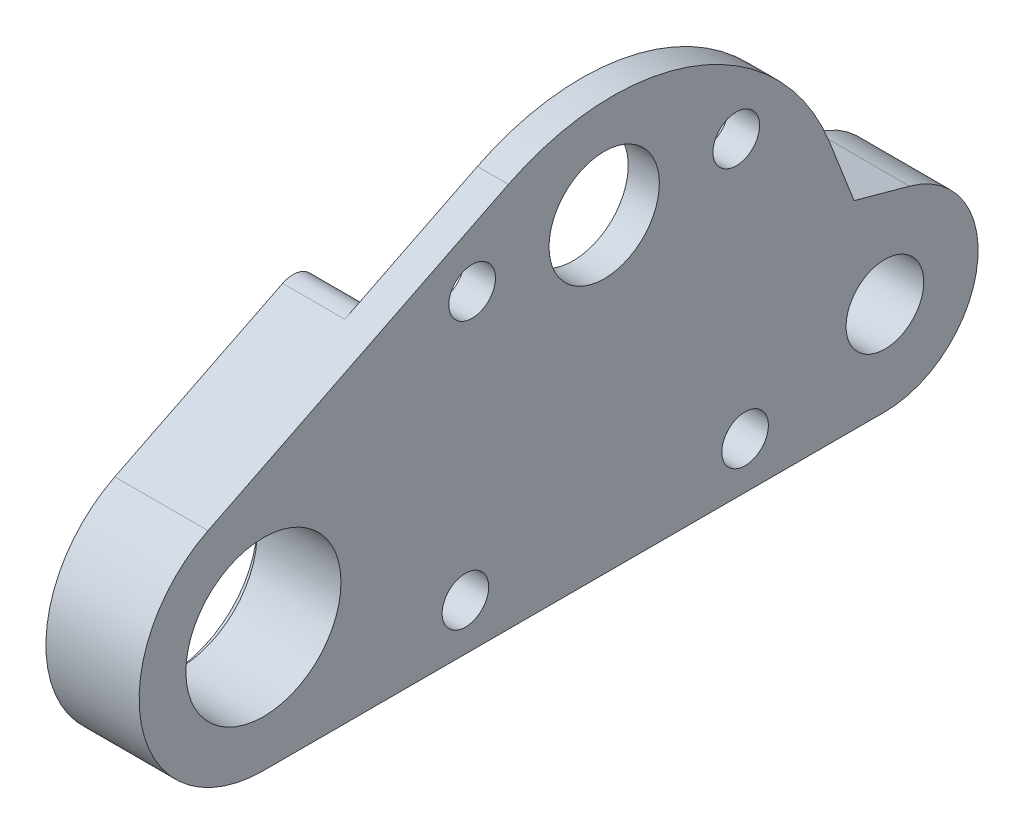
SolidWorks part; units mm, degrees
material "1060 Alloy"
ref_plane "Front Plane" through (0, 0, 0) normal (0, 0, 1) x (1, 0, 0)
ref_plane "Top Plane" through (0, 0, 0) normal (0, 1, 0) x (1, 0, 0)
ref_plane "Right Plane" through (0, 0, 0) normal (1, 0, 0) x (0, 0, -1)
sketch "Sketch27" plane through (0, 0, 0) normal (1, 0, 0) x (0, 0, -1)
  line L0 (6.4321, 49.1603) -> (25.768, 58.7953)
  line L1 (51.5869, 45.7863) -> (48.0144, 46.7661)
  line L3 (40.4317, 54) -> (23.4317, 54) construction
  line L5 (46.4319, 50.822) -> (48.0144, 46.7661)
  line L6 (50, 34) -> (10, 34)
  line L8 (0, 0) -> (60, 0) construction
  line L9 (0, 0) -> (0, 58) construction
  line L10 (0, 58) -> (60, 58) construction
  line L11 (60, 0) -> (60, 58) construction
  arc A0 (6.4321, 49.1603) -> (10, 34) centre (10, 42) ccw
  circle A1 centre (31.9317, 54) radius 12.5 construction
  arc A2 (46.4319, 50.822) -> (25.768, 58.7953) centre (32.4579, 45.3698) ccw
  circle A3 centre (31.9317, 54) radius 3.55
  arc A4 (51.5869, 45.7863) -> (50, 34) centre (50, 40) cw
  circle A5 centre (10, 42) radius 4.99
  circle A6 centre (50, 40) radius 2.5
  circle A7 centre (40.4317, 54) radius 1.5
  circle A8 centre (23.4317, 54) radius 1.5
  circle A9 centre (40.4317, 54) radius 3.25 construction
  circle A10 centre (23.4317, 54) radius 3.25 construction
  dimension "D9" = 6
  dimension "D10" = 5
  dimension "D11" = 15
  dimension "D12" = 9.98
  dimension "D13" = 8
  dimension "D15" = 25
  dimension "D6" = 25
  dimension "D17" = 7.1
  dimension "D16" = 3
  dimension "D19" = 6.5
  dimension "D1" = 60
  dimension "D2" = 58
  dimension "D3" = 42
  dimension "D4" = 10
  dimension "D5" = 40
  dimension "D7" = 50
  dimension "D8" = 12
  dimension "D18" = 8.5
extrude "Boss-Extrude1" add sketch "Sketch27" along normal blind 6
sketch "Sketch47" plane through (0, 0, 0) normal (-1, 0, 0) x (0, 0, 1)
  circle A0 centre (-10, 42) radius 5.605
  dimension "D1" = 11.21
extrude "Cut-Extrude8" cut sketch "Sketch47" against normal blind 0.6
sketch "Sketch48" plane through (0, 0, 0) normal (-1, 0, 0) x (0, 0, 1)
  line L1 (-25.768, 58.7953) -> (-6.4321, 49.1603) construction
  line L2 (-46.6832, 50.1781) -> (-40.4639, 66.1182)
  line L4 (-40.4639, 66.1182) -> (-17.2355, 54.5436)
  line L5 (-48.0144, 46.7661) -> (-46.4319, 50.822) construction
  arc A0 (-43.8601, 50.0991) -> (-19.402, 53.2863) centre (-31.9317, 54) ccw
  arc A1 (-43.8601, 50.0991) -> (-46.6832, 50.1781) centre (-45.2858, 49.6329) ccw
  arc A2 (-19.402, 53.2863) -> (-17.2355, 54.5436) centre (-17.9044, 53.201) cw
  dimension "D1" = 12.55
  dimension "D2" = 1.5
  dimension "D3" = 1.5
extrude "Cut-Extrude10" cut sketch "Sketch48" against normal blind 4
sketch "Sketch49" plane through (0, 0, 0) normal (-1, 0, 0) x (0, 0, 1)
  line L0 (-44, 34) -> (-20, 34)
  line L1 (-44, 34) -> (-44, 40)
  line L2 (-20, 34) -> (-20, 40)
  line L3 (-44, 40) -> (-20, 40)
  line L4 (-10, 34) -> (-50, 34) construction
  circle A0 centre (-50, 40) radius 2.5 construction
  dimension "D1" = 6
  dimension "D2" = 24
  dimension "D3" = 6
extrude "Cut-Extrude11" cut sketch "Sketch49" against normal blind 3
sketch "Sketch50" plane through (0, 0, 0) normal (-1, 0, 0) x (0, 0, 1)
  circle A0 centre (-44, 40) radius 1.5
  circle A1 centre (-20, 40) radius 1.5
  dimension "D1" = 3
extrude "Cut-Extrude12" cut sketch "Sketch50" against normal up to surface (3 mm away) up to face at (3, 37, -32)
fillet "Fillet1" radius 3 4 edges at (1.5, 38.5, -44) (1.5, 38.5, -20) (1.5, 40, -21.5) (1.5, 40, -42.5)
sketch "Sketch51" plane through (3, 0, 0) normal (-1, 0, 0) x (0, 0, 1)
  line L0 (-44, 34) -> (-20, 34) construction
  line L1 (-44, 36.6459) -> (-44, 34) construction
  line L2 (-20, 34) -> (-20, 36.6459) construction
  circle A0 centre (-41, 37) radius 1.5
  circle A1 centre (-23, 37) radius 1.5
  dimension "D1" = 3
  dimension "D2" = 3
  dimension "D3" = 3
  dimension "D4" = 3
  dimension "D5" = 3
extrude "Cut-Extrude13" cut sketch "Sketch51" against normal up to next
